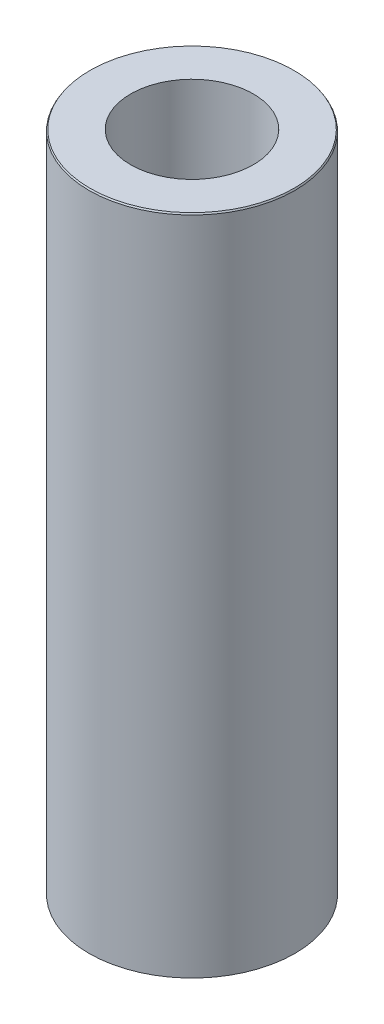
SolidWorks part; units mm, degrees
ref_plane "Front Plane" through (0, 0, 0) normal (0, 0, 1) x (1, 0, 0)
ref_plane "Top Plane" through (0, 0, 0) normal (0, 1, 0) x (1, 0, 0)
ref_plane "Right Plane" through (0, 0, 0) normal (1, 0, 0) x (0, 0, -1)
sketch "Sketch1" plane through (0, 0, 0) normal (0, 1, 0) x (1, 0, 0)
  circle A0 centre (0, 0) radius 47.5
  dimension "SHAFT_OD" = 95
extrude "Boss-Extrude1" add sketch "Sketch1" along normal blind 306.0371
sketch "Sketch2" plane through (0, 0, 0) normal (0, 1, 0) x (1, 0, 0)
  circle A0 centre (0, 0) radius 28.328
  dimension "BORE_D" = 56.656
extrude "Cut-Extrude1" cut sketch "Sketch2" along normal through all
chamfer "Chamfer1" distance 0.6849 angle 30 2 edges at (0, 306.0371, 47.5) (0, 0, 47.5) first distance on face at (0, 306.0371, 47.5) first distance on face at (0, 0, 28.328)
